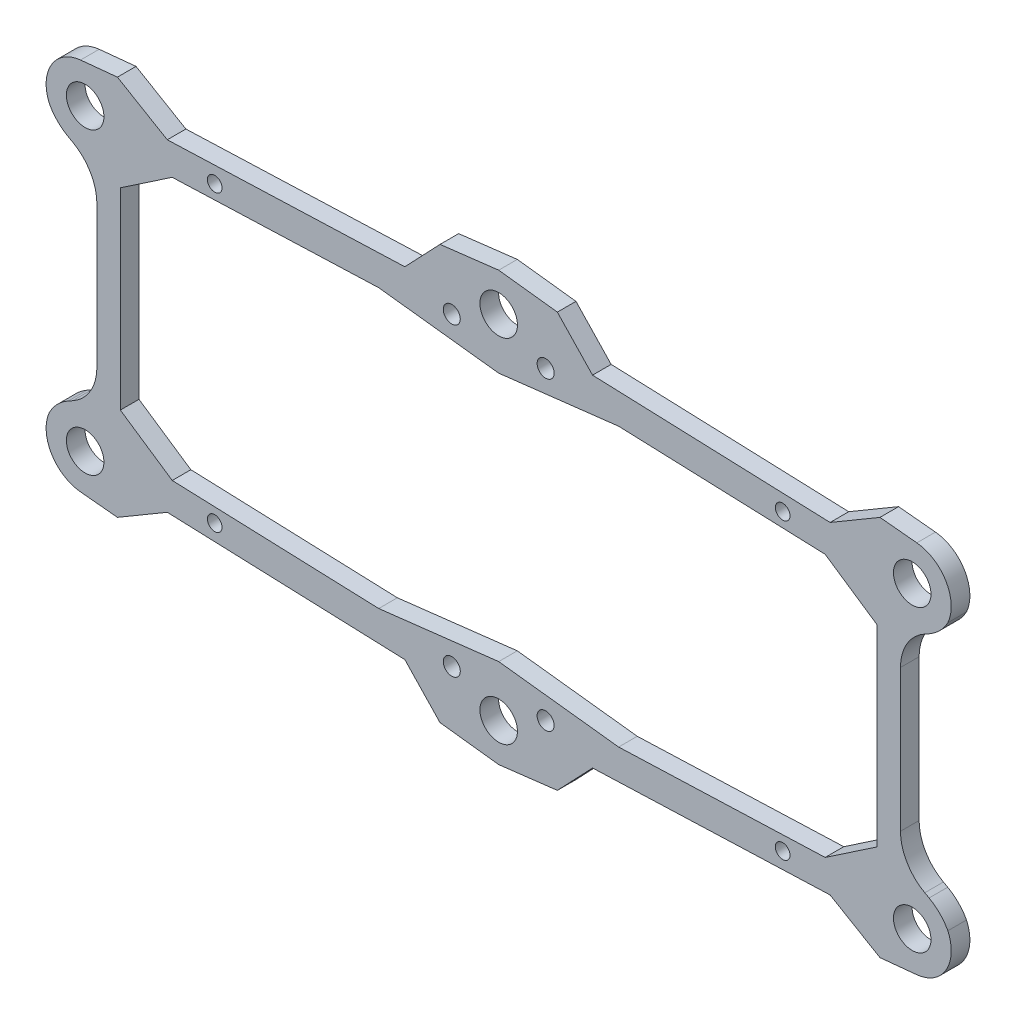
SolidWorks part; units mm, degrees
material "AISI 304"
ref_plane "Front Plane" through (0, 0, 0) normal (0, 0, 1) x (1, 0, 0)
ref_plane "Top Plane" through (0, 0, 0) normal (0, 1, 0) x (1, 0, 0)
ref_plane "Right Plane" through (0, 0, 0) normal (1, 0, 0) x (0, 0, -1)
sketch "Sketch1" plane through (0, 0, 0) normal (0, 0, 1) x (1, 0, 0)
  line L0 (0, 36.5) -> (-10, 35.3071)
  line L1 (-10, 35.3071) -> (-16, 29)
  line L2 (-16, 29) -> (-56.5, 27.5)
  line L3 (-56.5, 27.5) -> (-76.5, 14)
  line L4 (-76.5, 14) -> (-76.5, -14)
  line L5 (-87.0431, 0) -> (20.0163, 0) construction
  line L6 (0, 32.2788) -> (0, 0) construction
  line L7 (76.5, 14) -> (76.5, -14)
  line L8 (56.5, 27.5) -> (76.5, 14)
  line L9 (16, 29) -> (56.5, 27.5)
  line L10 (10, 35.3071) -> (16, 29)
  line L11 (0, 36.5) -> (10, 35.3071)
  line L12 (0, -36.5) -> (10, -35.3071)
  line L13 (10, -35.3071) -> (16, -29)
  line L14 (16, -29) -> (56.5, -27.5)
  line L15 (56.5, -27.5) -> (76.5, -14)
  line L16 (-56.5, -27.5) -> (-76.5, -14)
  line L17 (-16, -29) -> (-56.5, -27.5)
  line L18 (-10, -35.3071) -> (-16, -29)
  line L19 (0, -36.5) -> (-10, -35.3071)
  circle A0 centre (0, 30) radius 3.2
  circle A1 centre (-50, 0) radius 19.5 construction
  circle A2 centre (50, 0) radius 19.5 construction
  circle A3 centre (0, -30) radius 3.2
  point P35 (76.5, 0)
  point P36 (-76.5, 0)
  dimension "D1" = 6.4
  dimension "D2" = 39
  dimension "D3" = 60
  dimension "D4" = 100
  dimension "D5" = 153
  dimension "D6" = 73
  dimension "D7" = 28
  dimension "D8" = 55
  dimension "D9" = 20
  dimension "D10" = 32
  dimension "D11" = 20
  dimension "D12" = 58
extrude "Boss-Extrude1" add sketch "Sketch1" along normal blind 3.175
sketch "Sketch3" plane through (0, 0, 3.175) normal (0, 0, 1) x (1, 0, 0)
  line L0 (-56.5, 27.5) -> (-65, 32.5)
  line L1 (-56.5, 27.5) -> (-76.5, 14) construction
  line L2 (-65, 32.5) -> (-80.3, 31)
  line L3 (-80.3, 31) -> (-73.537, 16)
  line L4 (-73.537, 16) -> (-56.5, 27.5)
  line L5 (0, 0) -> (0, 46.5274) construction
  line L6 (73.537, 16) -> (56.5, 27.5)
  line L7 (80.3, 31) -> (73.537, 16)
  line L8 (65, 32.5) -> (80.3, 31)
  line L9 (56.5, 27.5) -> (65, 32.5)
  line L10 (0, 0) -> (-26.0239, 0) construction
  line L11 (56.5, -27.5) -> (65, -32.5)
  line L12 (65, -32.5) -> (80.3, -31)
  line L13 (80.3, -31) -> (73.537, -16)
  line L14 (73.537, -16) -> (56.5, -27.5)
  line L15 (-73.537, -16) -> (-56.5, -27.5)
  line L16 (-80.3, -31) -> (-73.537, -16)
  line L17 (-65, -32.5) -> (-80.3, -31)
  line L18 (-56.5, -27.5) -> (-65, -32.5)
  line L19 (-16, 29) -> (-56.5, 27.5) construction
  circle A0 centre (-70.5, 25.5) radius 3.2
  circle A1 centre (70.5, 25.5) radius 3.2
  circle A2 centre (-70.5, -25.5) radius 3.2
  circle A3 centre (70.5, -25.5) radius 3.2
  dimension "D1" = 6.4
  dimension "D2" = 70.5
  dimension "D3" = 25.5
  dimension "D4" = 62
  dimension "D5" = 65
  dimension "D6" = 65
  dimension "D7" = 80.3
  dimension "D8" = 32
extrude "Boss-Extrude2" add sketch "Sketch3" against normal up to surface (3.175 mm away) up to face at (3.2, 30, 0)
fillet "Fillet1" radius 6.5 4 edges at (-80.3, 31, 1.5875) (-80.3, -31, 1.5875) (80.3, -31, 1.5875) (80.3, 31, 1.5875)
sketch "Sketch6" plane through (0, 0, 0) normal (0, 0, -1) x (-1, 0, 0)
  circle A0 centre (8, 26) radius 1.45
  circle A1 centre (-8, 26) radius 1.45
  circle A2 centre (-8, -26) radius 1.45
  circle A3 centre (8, -26) radius 1.45
  dimension "D1" = 2.9
extrude "Cut-Extrude4" cut sketch "Sketch6" against normal through all
sketch "Sketch8" plane through (0, 0, 3.175) normal (0, 0, 1) x (1, 0, 0)
  line L0 (0, 0) -> (-91.0009, 0) construction
  line L1 (0, 0) -> (0, 46.3354) construction
  line L2 (-75.6901, 20.7753) -> (-68.5, 16.819)
  line L4 (-68.5, 16.819) -> (-68.5, -16.819)
  line L5 (-75.6901, 20.7753) -> (-83.4976, 20.7753)
  line L6 (-83.4976, 20.7753) -> (-83.4976, -20.7753)
  line L7 (-75.6901, -20.7753) -> (-83.4976, -20.7753)
  line L8 (-75.6901, -20.7753) -> (-68.5, -16.819)
  line L9 (75.6901, -20.7753) -> (68.5, -16.819)
  line L10 (75.6901, -20.7753) -> (83.4976, -20.7753)
  line L11 (83.4976, 20.7753) -> (83.4976, -20.7753)
  line L12 (75.6901, 20.7753) -> (83.4976, 20.7753)
  line L13 (68.5, 16.819) -> (68.5, -16.819)
  line L14 (75.6901, 20.7753) -> (68.5, 16.819)
  line L15 (-76.5773, 22.7431) -> (-73.537, 16) construction
  line L16 (-76.5, 14) -> (-76.5, -14) construction
  point P9 (68.5, 0)
  point P12 (-83.4976, 0)
  point P14 (-68.5, 0)
  point P15 (83.4976, 0)
  dimension "D1" = 8
extrude "Cut-Extrude14" cut sketch "Sketch8" against normal through all
sketch "Sketch7" plane through (0, 0, 3.175) normal (0, 0, 1) x (1, 0, 0)
  line L0 (0, 15.6961) -> (0, 0) construction
  line L1 (0, 0) -> (-17.6785, 0) construction
  line L2 (0, 21.2902) -> (-20.4496, 23.6817)
  line L12 (-20.4496, 23.6817) -> (-55.6556, 22.3777)
  line L13 (-55.6556, 22.3777) -> (-64.5, 16.4078)
  line L14 (-68.5, -16.819) -> (-68.5, 16.819) construction
  line L16 (-16, 29) -> (-56.5, 27.5) construction
  line L18 (-64.5, 16.4078) -> (-64.5, -16.4078)
  line L19 (64.5, 16.4078) -> (64.5, -16.4078)
  line L20 (55.6556, 22.3777) -> (64.5, 16.4078)
  line L21 (20.4496, 23.6817) -> (55.6556, 22.3777)
  line L22 (0, 21.2902) -> (20.4496, 23.6817)
  line L23 (0, -21.2902) -> (20.4496, -23.6817)
  line L24 (20.4496, -23.6817) -> (55.6556, -22.3777)
  line L25 (55.6556, -22.3777) -> (64.5, -16.4078)
  line L26 (-55.6556, -22.3777) -> (-64.5, -16.4078)
  line L27 (-20.4496, -23.6817) -> (-55.6556, -22.3777)
  line L28 (0, -21.2902) -> (-20.4496, -23.6817)
  point P16 (64.5, 0)
  point P17 (-64.5, 0)
  dimension "D1" = 5.15
  dimension "D2" = 4
extrude "Cut-Extrude13" cut sketch "Sketch7" against normal through all
fillet "Fillet2" radius 8 8 edges at (68.5, 16.819, 1.5875) (68.5, -16.819, 1.5875) (-68.5, -16.819, 1.5875) (-68.5, 16.819, 1.5875) (75.6901, 20.7753, 1.5875) (75.6901, -20.7753, 1.5875) (-75.6901, -20.7753, 1.5875) (-75.6901, 20.7753, 1.5875)
sketch "Sketch9" plane through (0, 0, 3.175) normal (0, 0, 1) x (1, 0, 0)
  line L0 (0, 17.6341) -> (0, 0) construction
  line L1 (0, 0) -> (-18.3275, 0) construction
  circle A0 centre (-48.4118, 25.0545) radius 1.25
  circle A1 centre (48.4118, 25.0545) radius 1.25
  circle A2 centre (-48.4118, -25.0545) radius 1.25
  circle A3 centre (48.4118, -25.0545) radius 1.25
  dimension "D1" = 2.5
extrude "Cut-Extrude15" cut sketch "Sketch9" against normal through all
